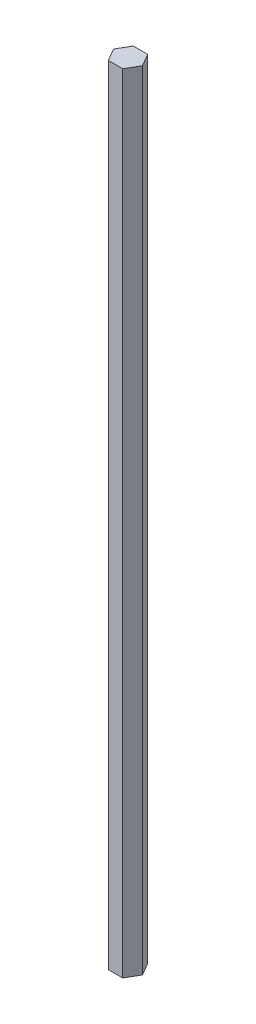
SolidWorks part; units mm, degrees
material "1023 Carbon Steel Sheet (SS)"
ref_plane "Front Plane" through (0, 0, 0) normal (0, 0, 1) x (1, 0, 0)
ref_plane "Top Plane" through (0, 0, 0) normal (0, 1, 0) x (1, 0, 0)
ref_plane "Right Plane" through (0, 0, 0) normal (1, 0, 0) x (0, 0, -1)
sketch "Sketch1" plane through (0, 0, 0) normal (0, 1, 0) x (1, 0, 0)
  line L7 (7.3323, 0) -> (3.6662, 6.35)
  line L8 (3.6662, 6.35) -> (-3.6662, 6.35)
  line L9 (-3.6662, 6.35) -> (-7.3323, 0)
  line L10 (-7.3323, 0) -> (-3.6662, -6.35)
  line L11 (-3.6662, -6.35) -> (3.6662, -6.35)
  line L12 (3.6662, -6.35) -> (7.3323, 0)
  circle A0 centre (0, 0) radius 6.35 construction
  dimension "D1" = 12.7
extrude "Boss-Extrude1" add sketch "Sketch1" along normal mid plane 400
ref_axis "Axis1" through (0, 273.0375, 0) along (0, -1, 0)
